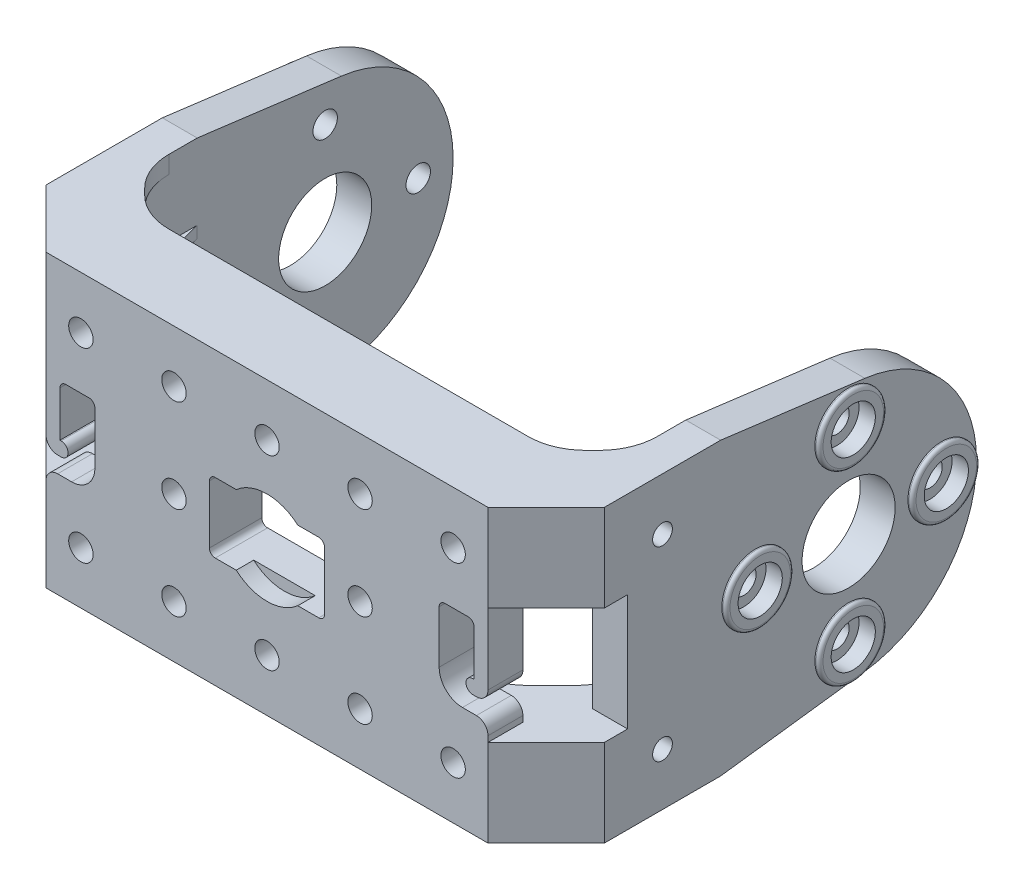
SolidWorks part; units mm, degrees
material "ABS PC"
ref_plane "Front Plane" through (0, 0, 0) normal (0, 0, 1) x (1, 0, 0)
ref_plane "Top Plane" through (0, 0, 0) normal (0, 1, 0) x (1, 0, 0)
ref_plane "Right Plane" through (0, 0, 0) normal (1, 0, 0) x (0, 0, -1)
ref_plane "Plane1" through (0, 0, 23) normal (0, 0, 1) x (1, 0, 0)
sketch "Sketch1" plane through (0, 0, 23) normal (0, 0, 1) x (1, 0, 0)
  line L0 (-14.5956, -5) -> (10.0809, -5)
  line L1 (10.0809, -5) -> (10.0809, -2.4936)
  line L2 (10.0809, -2.4936) -> (11.2, -1.8475)
  line L3 (11.2, -1.8475) -> (11.2, 1.8475)
  line L4 (11.2, 1.8475) -> (10.0809, 2.4936)
  line L5 (10.0809, 2.4936) -> (10.0809, 3.5)
  line L6 (10.0809, 3.5) -> (14.5956, 5)
  line L7 (14.5956, 5) -> (-14.5956, 5)
  line L8 (-14.5956, 5) -> (-10.0809, 3.5)
  line L9 (-10.0809, 3.5) -> (-10.0809, 2.4936)
  line L10 (-10.0809, 2.4936) -> (-11.2, 1.8475)
  line L11 (-11.2, 1.8475) -> (-11.2, -1.8475)
  line L12 (-11.2, -1.8475) -> (-10.0809, -2.4936)
  line L13 (-10.0809, -2.4936) -> (-10.0809, -3.5)
  line L14 (-10.0809, -3.5) -> (-14.5956, -5)
extrude "Boss-Extrude1" add sketch "Sketch1" against normal blind 1
sketch "Sketch2" plane through (0, 0, 22) normal (0, 0, -1) x (-1, 0, 0)
  line L0 (-10.0809, -5) -> (-10.0809, 3.5)
  line L1 (-10.0809, 3.5) -> (-14.5956, 5)
  line L2 (-14.5956, 5) -> (14.5956, 5)
  line L3 (14.5956, 5) -> (10.0809, 3.5)
  line L4 (10.0809, 3.5) -> (10.0809, -3.5)
  line L5 (10.0809, -3.5) -> (14.5956, -5)
  line L6 (14.5956, -5) -> (-10.0809, -5)
extrude "Boss-Extrude2" add sketch "Sketch2" along normal blind 0.5
sketch "Sketch3" plane through (0, 0, 23) normal (0, 0, 1) x (1, 0, 0)
  line L0 (-8.3378, -3.5) -> (-10.0809, -2.4936)
  line L1 (-10.0809, -2.4936) -> (-10.0809, -3.5)
  line L2 (-10.0809, -3.5) -> (-8.3378, -3.5)
extrude "Cut-Extrude1" cut sketch "Sketch3" against normal blind 1
sketch "Sketch4" plane through (0, 0, 23) normal (0, 0, 1) x (1, 0, 0)
  line L0 (-10.0809, 2.4936) -> (-8.3378, 3.5)
  line L1 (-8.3378, 3.5) -> (-10.0809, 3.5)
  line L2 (-10.0809, 3.5) -> (-10.0809, 2.4936)
extrude "Cut-Extrude2" cut sketch "Sketch4" against normal blind 1
sketch "Sketch5" plane through (0, 0, 23) normal (0, 0, 1) x (1, 0, 0)
  line L0 (10.0809, -2.4936) -> (8.3378, -3.5)
  line L1 (8.3378, -3.5) -> (10.0809, -3.5)
  line L2 (10.0809, -3.5) -> (10.0809, -2.4936)
extrude "Cut-Extrude3" cut sketch "Sketch5" against normal blind 1
sketch "Sketch6" plane through (10.0809, 0, 0) normal (1, 0, 0) x (0, 0, -1)
  line L0 (-23, -5) -> (-23, -3.5)
  line L1 (-23, -3.5) -> (-21.5, -3.5)
  line L2 (-21.5, -3.5) -> (-21.5, -5)
  line L3 (-21.5, -5) -> (-23, -5)
extrude "Boss-Extrude3" add sketch "Sketch6" along normal blind 10.9191
sketch "Sketch7" plane through (0, 0, 23) normal (0, 0, 1) x (1, 0, 0)
  line L0 (8.3378, 3.5) -> (10.0809, 2.4936)
  line L1 (10.0809, 2.4936) -> (10.0809, 3.5)
  line L2 (10.0809, 3.5) -> (8.3378, 3.5)
extrude "Cut-Extrude4" cut sketch "Sketch7" against normal blind 1
sketch "Sketch8" plane through (0, -5, 0) normal (0, -1, 0) x (1, 0, 0)
  line L0 (-21, 11) -> (-21, 23)
  line L1 (-21, 23) -> (21, 23)
  line L2 (21, 23) -> (21, 11)
  line L3 (21, 11) -> (19.5, 17.0147)
  line L4 (19.5, 17.0147) -> (17.5147, 19)
  line L5 (17.5147, 19) -> (-17.5147, 19)
  line L6 (-17.5147, 19) -> (-19.5, 17.0147)
  line L7 (-19.5, 17.0147) -> (-21, 11)
extrude "Boss-Extrude4" add sketch "Sketch8" along normal blind 7.5
sketch "Sketch9" plane through (0, 5, 0) normal (0, 1, 0) x (-1, 0, 0)
  line L0 (21, 23) -> (21, 11)
  line L1 (21, 11) -> (19.5, 17.0147)
  line L2 (19.5, 17.0147) -> (17.5147, 19)
  line L3 (17.5147, 19) -> (-17.5147, 19)
  line L4 (-17.5147, 19) -> (-19.5, 17.0147)
  line L5 (-19.5, 17.0147) -> (-21, 11)
  line L6 (-21, 11) -> (-21, 23)
  line L7 (-21, 23) -> (21, 23)
extrude "Boss-Extrude5" add sketch "Sketch9" along normal blind 7.5
sketch "Sketch10" plane through (0, -5, 0) normal (0, 1, 0) x (-1, 0, 0)
  line L0 (-17.5147, 19) -> (17.5147, 19)
  line L1 (17.5147, 19) -> (15.0147, 21.5)
  line L2 (15.0147, 21.5) -> (-15.0147, 21.5)
  line L3 (-15.0147, 21.5) -> (-17.5147, 19)
extrude "Cut-Extrude5" cut sketch "Sketch10" against normal blind 6
sketch "Sketch11" plane through (0, 5, 0) normal (0, -1, 0) x (1, 0, 0)
  line L0 (-17.5147, 19) -> (17.5147, 19)
  line L1 (17.5147, 19) -> (15.0147, 21.5)
  line L2 (15.0147, 21.5) -> (-15.0147, 21.5)
  line L3 (-15.0147, 21.5) -> (-17.5147, 19)
extrude "Cut-Extrude6" cut sketch "Sketch11" against normal blind 6
sketch "Sketch12" plane through (-21, 0, 0) normal (-1, 0, 0) x (0, 0, 1)
  line L0 (23, 12.5) -> (23, 5)
  line L1 (23, 5) -> (19, 5)
  line L2 (19, 5) -> (19, -5)
  line L3 (19, -5) -> (23, -5)
  line L4 (23, -5) -> (23, -12.5)
  line L5 (23, -12.5) -> (11, -12.5)
  line L6 (11, -12.5) -> (-1.3986, -10.9107)
  line L7 (-1.3986, 10.9107) -> (11, 12.5)
  line L8 (11, 12.5) -> (23, 12.5)
  arc A0 (-1.3986, -10.9107) -> (-1.3986, 10.9107) centre (0, 0) cw
extrude "Boss-Extrude6" add sketch "Sketch12" along normal blind 3
sketch "Sketch13" plane through (21, 0, 0) normal (1, 0, 0) x (0, 0, -1)
  line L0 (-23, 12.5) -> (-11, 12.5)
  line L1 (-11, 12.5) -> (1.3986, 10.9107)
  line L2 (1.3986, -10.9107) -> (-11, -12.5)
  line L3 (-11, -12.5) -> (-23, -12.5)
  line L4 (-23, -12.5) -> (-23, -3.5)
  line L5 (-23, -3.5) -> (-21.5, -3.5)
  line L6 (-21.5, -3.5) -> (-21.5, -5)
  line L7 (-21.5, -5) -> (-19, -5)
  line L8 (-19, -5) -> (-19, 5)
  line L9 (-19, 5) -> (-23, 5)
  line L10 (-23, 5) -> (-23, 12.5)
  arc A0 (1.3986, 10.9107) -> (1.3986, -10.9107) centre (0, 0) cw
extrude "Boss-Extrude7" add sketch "Sketch13" along normal blind 3
sketch "Sketch14" plane through (0, 12.5, 0) normal (0, 1, 0) x (-1, 0, 0)
  line L0 (21, 11) -> (21, 15.5147)
  line L1 (21, 15.5147) -> (19.5, 17.0147)
  line L2 (19.5, 17.0147) -> (21, 11)
extrude "Cut-Extrude7" cut sketch "Sketch14" against normal blind 1.5
sketch "Sketch15" plane through (0, 12.5, 0) normal (0, 1, 0) x (-1, 0, 0)
  line L0 (-21, 11) -> (-19.5, 17.0147)
  line L1 (-19.5, 17.0147) -> (-21, 15.5147)
  line L2 (-21, 15.5147) -> (-21, 11)
extrude "Cut-Extrude8" cut sketch "Sketch15" against normal blind 1.5
sketch "Sketch16" plane through (0, 11, 0) normal (0, 1, 0) x (-1, 0, 0)
  line L0 (21, 22) -> (-21, 22)
  line L1 (-21, 22) -> (-21, 11)
  line L2 (-21, 11) -> (-19.5, 17.0147)
  line L3 (-19.5, 17.0147) -> (-15.0147, 21.5)
  line L4 (-15.0147, 21.5) -> (15.0147, 21.5)
  line L5 (15.0147, 21.5) -> (19.5, 17.0147)
  line L6 (19.5, 17.0147) -> (21, 11)
  line L7 (21, 11) -> (21, 22)
extrude "Cut-Extrude9" cut sketch "Sketch16" against normal blind 5
sketch "Sketch17" plane through (10.0809, 0, 0) normal (1, 0, 0) x (0, 0, -1)
  line L0 (-21.5, 3.5) -> (-22, 3.5)
  line L1 (-22, 3.5) -> (-22, -3.5)
  line L2 (-22, -3.5) -> (-21.5, -3.5)
  line L3 (-21.5, -3.5) -> (-21.5, 3.5)
extrude "Cut-Extrude10" cut sketch "Sketch17" against normal blind 1.7431
sketch "Sketch18" plane through (0, -12.5, 0) normal (0, -1, 0) x (1, 0, 0)
  line L0 (-19.5, 17.0147) -> (-21, 15.5147)
  line L1 (-21, 15.5147) -> (-21, 11)
  line L2 (-21, 11) -> (-19.5, 17.0147)
extrude "Cut-Extrude11" cut sketch "Sketch18" against normal blind 1.5
sketch "Sketch19" plane through (0, -12.5, 0) normal (0, -1, 0) x (1, 0, 0)
  line L0 (21, 15.5147) -> (19.5, 17.0147)
  line L1 (19.5, 17.0147) -> (21, 11)
  line L2 (21, 11) -> (21, 15.5147)
extrude "Cut-Extrude12" cut sketch "Sketch19" against normal blind 1.5
sketch "Sketch20" plane through (0, -11, 0) normal (0, -1, 0) x (1, 0, 0)
  line L0 (21, 22) -> (-21, 22)
  line L1 (-21, 22) -> (-21, 11)
  line L2 (-21, 11) -> (-19.5, 17.0147)
  line L3 (-19.5, 17.0147) -> (-15.0147, 21.5)
  line L4 (-15.0147, 21.5) -> (15.0147, 21.5)
  line L5 (15.0147, 21.5) -> (19.5, 17.0147)
  line L6 (19.5, 17.0147) -> (21, 11)
  line L7 (21, 11) -> (21, 22)
extrude "Cut-Extrude13" cut sketch "Sketch20" against normal blind 5
sketch "Sketch21" plane through (8.3378, 0, 0) normal (1, 0, 0) x (0, 0, -1)
  line L0 (-21.5, 3.5) -> (-22, 3.5)
  line L1 (-22, 3.5) -> (-22, -3.5)
  line L2 (-22, -3.5) -> (-21.5, -3.5)
  line L3 (-21.5, -3.5) -> (-21.5, 3.5)
extrude "Cut-Extrude14" cut sketch "Sketch21" against normal blind 2.3378
sketch "Sketch22" plane through (-10.0809, 0, 0) normal (-1, 0, 0) x (0, 0, 1)
  line L0 (21.5, -3.5) -> (22, -3.5)
  line L1 (22, -3.5) -> (22, 3.5)
  line L2 (22, 3.5) -> (21.5, 3.5)
  line L3 (21.5, 3.5) -> (21.5, -3.5)
extrude "Cut-Extrude15" cut sketch "Sketch22" against normal blind 1.7431
sketch "Sketch23" plane through (24, 0, 0) normal (1, 0, 0) x (0, 0, -1)
  line L0 (-21.5, -3.5) -> (-23, -3.5)
  line L1 (-23, -3.5) -> (-23, -5)
  line L2 (-23, -5) -> (-21.5, -5)
  line L3 (-21.5, -5) -> (-21.5, -3.5)
extrude "Cut-Extrude16" cut sketch "Sketch23" against normal blind 8.9853
sketch "Sketch24" plane through (-8.3378, 0, 0) normal (-1, 0, 0) x (0, 0, 1)
  line L0 (21.5, -3.5) -> (22, -3.5)
  line L1 (22, -3.5) -> (22, 3.5)
  line L2 (22, 3.5) -> (21.5, 3.5)
  line L3 (21.5, 3.5) -> (21.5, -3.5)
extrude "Cut-Extrude17" cut sketch "Sketch24" against normal blind 2.3378
sketch "Sketch25" plane through (15.0147, 0, 0) normal (1, 0, 0) x (0, 0, -1)
  line L0 (-21.5, -3.5) -> (-23, -3.5)
  line L1 (-23, -3.5) -> (-23, -5)
  line L2 (-23, -5) -> (-21.5, -5)
  line L3 (-21.5, -5) -> (-21.5, -3.5)
extrude "Cut-Extrude18" cut sketch "Sketch25" against normal blind 0.4191
sketch "Sketch26" plane through (0, 0, 23) normal (0, 0, 1) x (1, 0, 0)
  line L0 (14.8, 3.5) -> (14.8, -3.5)
  line L1 (14.8, -3.5) -> (19, -3.5)
  line L2 (19, -3.5) -> (19, -5)
  line L3 (19, -5) -> (24, -5)
  line L4 (24, -5) -> (24, -12.5)
  line L5 (24, -12.5) -> (-24, -12.5)
  line L6 (-24, -12.5) -> (-24, -5)
  line L7 (-24, -5) -> (-19, -5)
  line L8 (-19, -5) -> (-19, -3.5)
  line L9 (-19, -3.5) -> (-14.8, -3.5)
  line L10 (-14.8, -3.5) -> (-14.8, 3.5)
  line L11 (-14.8, 3.5) -> (-17.8, 3.5)
  line L12 (-17.8, 3.5) -> (-17.8, -0.9)
  line L13 (-17.8, -0.9) -> (-17.7, -0.9)
  line L14 (-17.7, -2.1) -> (-19, -2.1)
  line L15 (-19, -2.1) -> (-19, 5)
  line L16 (-19, 5) -> (-24, 5)
  line L17 (-24, 5) -> (-24, 12.5)
  line L18 (-24, 12.5) -> (24, 12.5)
  line L19 (24, 12.5) -> (24, 5)
  line L20 (24, 5) -> (19, 5)
  line L21 (19, 5) -> (19, -2.1)
  line L22 (19, -2.1) -> (17.7, -2.1)
  line L23 (17.7, -0.9) -> (17.8, -0.9)
  line L24 (17.8, -0.9) -> (17.8, 3.5)
  line L25 (17.8, 3.5) -> (14.8, 3.5)
  arc A0 (-17.7, -0.9) -> (-17.7, -2.1) centre (-17.7, -1.5) cw
  arc A1 (17.7, -2.1) -> (17.7, -0.9) centre (17.7, -1.5) cw
extrude "Boss-Extrude8" add sketch "Sketch26" along normal blind 3
sketch "Sketch27" plane through (0, 0, 21.5) normal (0, 0, -1) x (-1, 0, 0)
  line L0 (-9.9191, 4.5) -> (9.9191, 4.5)
  line L1 (9.9191, 4.5) -> (14.4338, 6)
  line L2 (14.4338, 6) -> (-14.4338, 6)
  line L3 (-14.4338, 6) -> (-9.9191, 4.5)
extrude "Cut-Extrude19" cut sketch "Sketch27" against normal blind 0.5
sketch "Sketch28" plane through (0, 0, 22) normal (0, 0, -1) x (-1, 0, 0)
  line L0 (9.9191, 4.5) -> (13.8102, 5.7928)
  line L1 (13.8102, 5.7928) -> (12.5359, 8)
  line L2 (12.5359, 8) -> (14.2679, 11)
  line L3 (14.2679, 11) -> (9.2038, 11)
  line L4 (9.2038, 11) -> (11.2, 9.8475)
  line L5 (11.2, 9.8475) -> (11.2, 6.1525)
  line L6 (11.2, 6.1525) -> (8.3378, 4.5)
  line L7 (8.3378, 4.5) -> (9.9191, 4.5)
extrude "Cut-Extrude20" cut sketch "Sketch28" against normal blind 1
sketch "Sketch29" plane through (0, 0, 22) normal (0, 0, -1) x (-1, 0, 0)
  line L0 (7.6622, 4.5) -> (4.8, 6.1525)
  line L1 (4.8, 6.1525) -> (4.8, 9.8475)
  line L2 (4.8, 9.8475) -> (6.7962, 11)
  line L3 (6.7962, 11) -> (1.2038, 11)
  line L4 (1.2038, 11) -> (3.2, 9.8475)
  line L5 (3.2, 9.8475) -> (3.2, 6.1525)
  line L6 (3.2, 6.1525) -> (0.3378, 4.5)
  line L7 (0.3378, 4.5) -> (7.6622, 4.5)
extrude "Cut-Extrude21" cut sketch "Sketch29" against normal blind 1
sketch "Sketch30" plane through (0, 0, 22) normal (0, 0, -1) x (-1, 0, 0)
  line L0 (-8.3378, 4.5) -> (-11.2, 6.1525)
  line L1 (-11.2, 6.1525) -> (-11.2, 9.8475)
  line L2 (-11.2, 9.8475) -> (-9.2038, 11)
  line L3 (-9.2038, 11) -> (-14.2679, 11)
  line L4 (-14.2679, 11) -> (-12.5359, 8)
  line L5 (-12.5359, 8) -> (-13.8102, 5.7928)
  line L6 (-13.8102, 5.7928) -> (-9.9191, 4.5)
  line L7 (-9.9191, 4.5) -> (-8.3378, 4.5)
extrude "Cut-Extrude22" cut sketch "Sketch30" against normal blind 1
sketch "Sketch31" plane through (0, 0, 21.5) normal (0, 0, -1) x (-1, 0, 0)
  line L0 (9.9191, -4.5) -> (-9.9191, -4.5)
  line L1 (-9.9191, -4.5) -> (-14.4338, -6)
  line L2 (-14.4338, -6) -> (14.4338, -6)
  line L3 (14.4338, -6) -> (9.9191, -4.5)
extrude "Cut-Extrude23" cut sketch "Sketch31" against normal blind 0.5
sketch "Sketch32" plane through (0, 0, 22) normal (0, 0, -1) x (-1, 0, 0)
  line L0 (-7.6622, -4.5) -> (-4.8, -6.1525)
  line L1 (-4.8, -6.1525) -> (-4.8, -9.8475)
  line L2 (-4.8, -9.8475) -> (-6.7962, -11)
  line L3 (-6.7962, -11) -> (-1.2038, -11)
  line L4 (-1.2038, -11) -> (-3.2, -9.8475)
  line L5 (-3.2, -9.8475) -> (-3.2, -6.1525)
  line L6 (-3.2, -6.1525) -> (-0.3378, -4.5)
  line L7 (-0.3378, -4.5) -> (-7.6622, -4.5)
extrude "Cut-Extrude24" cut sketch "Sketch32" against normal blind 1
sketch "Sketch33" plane through (0, 0, 22) normal (0, 0, -1) x (-1, 0, 0)
  line L0 (-9.9191, -4.5) -> (-13.8102, -5.7928)
  line L1 (-13.8102, -5.7928) -> (-12.5359, -8)
  line L2 (-12.5359, -8) -> (-14.2679, -11)
  line L3 (-14.2679, -11) -> (-9.2038, -11)
  line L4 (-9.2038, -11) -> (-11.2, -9.8475)
  line L5 (-11.2, -9.8475) -> (-11.2, -6.1525)
  line L6 (-11.2, -6.1525) -> (-8.3378, -4.5)
  line L7 (-8.3378, -4.5) -> (-9.9191, -4.5)
extrude "Cut-Extrude25" cut sketch "Sketch33" against normal blind 1
sketch "Sketch34" plane through (0, 0, 22) normal (0, 0, -1) x (-1, 0, 0)
  line L0 (-0.3378, 4.5) -> (-3.2, 6.1525)
  line L1 (-3.2, 6.1525) -> (-3.2, 9.8475)
  line L2 (-3.2, 9.8475) -> (-1.2038, 11)
  line L3 (-1.2038, 11) -> (-6.7962, 11)
  line L4 (-6.7962, 11) -> (-4.8, 9.8475)
  line L5 (-4.8, 9.8475) -> (-4.8, 6.1525)
  line L6 (-4.8, 6.1525) -> (-7.6622, 4.5)
  line L7 (-7.6622, 4.5) -> (-0.3378, 4.5)
extrude "Cut-Extrude26" cut sketch "Sketch34" against normal blind 1
sketch "Sketch35" plane through (0, 0, 22) normal (0, 0, -1) x (-1, 0, 0)
  line L0 (8.3378, -4.5) -> (11.2, -6.1525)
  line L1 (11.2, -6.1525) -> (11.2, -9.8475)
  line L2 (11.2, -9.8475) -> (9.2038, -11)
  line L3 (9.2038, -11) -> (14.2679, -11)
  line L4 (14.2679, -11) -> (12.5359, -8)
  line L5 (12.5359, -8) -> (13.8102, -5.7928)
  line L6 (13.8102, -5.7928) -> (9.9191, -4.5)
  line L7 (9.9191, -4.5) -> (8.3378, -4.5)
extrude "Cut-Extrude27" cut sketch "Sketch35" against normal blind 1
sketch "Sketch36" plane through (0, 0, 22) normal (0, 0, -1) x (-1, 0, 0)
  line L0 (0.3378, -4.5) -> (3.2, -6.1525)
  line L1 (3.2, -6.1525) -> (3.2, -9.8475)
  line L2 (3.2, -9.8475) -> (1.2038, -11)
  line L3 (1.2038, -11) -> (6.7962, -11)
  line L4 (6.7962, -11) -> (4.8, -9.8475)
  line L5 (4.8, -9.8475) -> (4.8, -6.1525)
  line L6 (4.8, -6.1525) -> (7.6622, -4.5)
  line L7 (7.6622, -4.5) -> (0.3378, -4.5)
extrude "Cut-Extrude28" cut sketch "Sketch36" against normal blind 1
sketch "Sketch37" plane through (0, 0, 22) normal (0, 0, -1) x (-1, 0, 0)
  line L0 (-13.6906, -8) -> (-14.8453, -6)
  line L1 (-14.8453, -6) -> (-17.1547, -6)
  line L2 (-17.1547, -6) -> (-18.3094, -8)
  line L3 (-18.3094, -8) -> (-17.1547, -10)
  line L4 (-17.1547, -10) -> (-14.8453, -10)
  line L5 (-14.8453, -10) -> (-13.6906, -8)
extrude "Cut-Extrude29" cut sketch "Sketch37" against normal blind 2
sketch "Sketch38" plane through (0, 0, 22) normal (0, 0, -1) x (-1, 0, 0)
  line L0 (-17.7321, -11) -> (-19.4641, -8)
  line L1 (-19.4641, -8) -> (-18.3094, -6)
  line L2 (-18.3094, -6) -> (-21, -6)
  line L3 (-21, -6) -> (-21, -11)
  line L4 (-21, -11) -> (-17.7321, -11)
extrude "Cut-Extrude30" cut sketch "Sketch38" against normal blind 1
sketch "Sketch39" plane through (0, 0, 22) normal (0, 0, -1) x (-1, 0, 0)
  line L0 (-14.8453, 10) -> (-17.1547, 10)
  line L1 (-17.1547, 10) -> (-18.3094, 8)
  line L2 (-18.3094, 8) -> (-17.1547, 6)
  line L3 (-17.1547, 6) -> (-14.8453, 6)
  line L4 (-14.8453, 6) -> (-13.6906, 8)
  line L5 (-13.6906, 8) -> (-14.8453, 10)
extrude "Cut-Extrude31" cut sketch "Sketch39" against normal blind 2
sketch "Sketch40" plane through (0, 0, 22) normal (0, 0, -1) x (-1, 0, 0)
  line L0 (-17.7321, 11) -> (-21, 11)
  line L1 (-21, 11) -> (-21, 6)
  line L2 (-21, 6) -> (-18.3094, 6)
  line L3 (-18.3094, 6) -> (-19.4641, 8)
  line L4 (-19.4641, 8) -> (-17.7321, 11)
extrude "Cut-Extrude32" cut sketch "Sketch40" against normal blind 1
sketch "Sketch41" plane through (0, 0, 22) normal (0, 0, -1) x (-1, 0, 0)
  line L0 (13.6906, 8) -> (14.8453, 6)
  line L1 (14.8453, 6) -> (17.1547, 6)
  line L2 (17.1547, 6) -> (18.3094, 8)
  line L3 (18.3094, 8) -> (17.1547, 10)
  line L4 (17.1547, 10) -> (14.8453, 10)
  line L5 (14.8453, 10) -> (13.6906, 8)
extrude "Cut-Extrude33" cut sketch "Sketch41" against normal blind 2
sketch "Sketch42" plane through (0, 0, 22) normal (0, 0, -1) x (-1, 0, 0)
  line L0 (17.7321, 11) -> (19.4641, 8)
  line L1 (19.4641, 8) -> (18.3094, 6)
  line L2 (18.3094, 6) -> (21, 6)
  line L3 (21, 6) -> (21, 11)
  line L4 (21, 11) -> (17.7321, 11)
extrude "Cut-Extrude34" cut sketch "Sketch42" against normal blind 1
sketch "Sketch43" plane through (0, 0, 22) normal (0, 0, -1) x (-1, 0, 0)
  line L0 (14.8453, -10) -> (17.1547, -10)
  line L1 (17.1547, -10) -> (18.3094, -8)
  line L2 (18.3094, -8) -> (17.1547, -6)
  line L3 (17.1547, -6) -> (14.8453, -6)
  line L4 (14.8453, -6) -> (13.6906, -8)
  line L5 (13.6906, -8) -> (14.8453, -10)
extrude "Cut-Extrude35" cut sketch "Sketch43" against normal blind 2
sketch "Sketch44" plane through (0, 0, 22) normal (0, 0, -1) x (-1, 0, 0)
  line L0 (17.7321, -11) -> (21, -11)
  line L1 (21, -11) -> (21, -6)
  line L2 (21, -6) -> (18.3094, -6)
  line L3 (18.3094, -6) -> (19.4641, -8)
  line L4 (19.4641, -8) -> (17.7321, -11)
extrude "Cut-Extrude36" cut sketch "Sketch44" against normal blind 1
sketch "Sketch45" plane through (0, 0, 22) normal (0, 0, -1) x (-1, 0, 0)
  line L0 (-8, 2.3094) -> (-10, 1.1547)
  line L1 (-10, 1.1547) -> (-10, -1.1547)
  line L2 (-10, -1.1547) -> (-8, -2.3094)
  line L3 (-8, -2.3094) -> (-6, -1.1547)
  line L4 (-6, -1.1547) -> (-6, 1.1547)
  line L5 (-6, 1.1547) -> (-8, 2.3094)
extrude "Cut-Extrude37" cut sketch "Sketch45" against normal blind 2
sketch "Sketch46" plane through (0, 0, 22) normal (0, 0, -1) x (-1, 0, 0)
  line L0 (-6, 3.5) -> (-7.6622, 3.5)
  line L1 (-7.6622, 3.5) -> (-6, 2.5403)
  line L2 (-6, 2.5403) -> (-6, 3.5)
extrude "Cut-Extrude38" cut sketch "Sketch46" against normal blind 1
sketch "Sketch47" plane through (0, 0, 22) normal (0, 0, -1) x (-1, 0, 0)
  line L0 (-6, -2.5403) -> (-7.6622, -3.5)
  line L1 (-7.6622, -3.5) -> (-6, -3.5)
  line L2 (-6, -3.5) -> (-6, -2.5403)
extrude "Cut-Extrude39" cut sketch "Sketch47" against normal blind 1
sketch "Sketch48" plane through (0, 0, 22) normal (0, 0, -1) x (-1, 0, 0)
  line L0 (8, 2.3094) -> (6, 1.1547)
  line L1 (6, 1.1547) -> (6, -1.1547)
  line L2 (6, -1.1547) -> (8, -2.3094)
  line L3 (8, -2.3094) -> (10, -1.1547)
  line L4 (10, -1.1547) -> (10, 1.1547)
  line L5 (10, 1.1547) -> (8, 2.3094)
extrude "Cut-Extrude40" cut sketch "Sketch48" against normal blind 2
sketch "Sketch49" plane through (0, 0, 22) normal (0, 0, -1) x (-1, 0, 0)
  line L0 (6, -3.5) -> (7.6622, -3.5)
  line L1 (7.6622, -3.5) -> (6, -2.5403)
  line L2 (6, -2.5403) -> (6, -3.5)
extrude "Cut-Extrude41" cut sketch "Sketch49" against normal blind 1
sketch "Sketch50" plane through (0, 0, 22) normal (0, 0, -1) x (-1, 0, 0)
  line L0 (6, 2.5403) -> (7.6622, 3.5)
  line L1 (7.6622, 3.5) -> (6, 3.5)
  line L2 (6, 3.5) -> (6, 2.5403)
extrude "Cut-Extrude42" cut sketch "Sketch50" against normal blind 1
sketch "Sketch51" plane through (0, 0, 26) normal (0, 0, 1) x (1, 0, 0)
  line L0 (-4.95, 3) -> (-4.95, -3)
  line L1 (-4.95, -3) -> (4.95, -3)
  line L2 (4.95, -3) -> (4.95, 3)
  line L3 (4.95, 3) -> (-4.95, 3)
extrude "Cut-Extrude43" cut sketch "Sketch51" against normal through all
sketch "Sketch52" plane through (0, 0, 26) normal (0, 0, 1) x (1, 0, 0)
  line L0 (2.6458, -3) -> (-2.6458, -3)
  arc A0 (-2.6458, -3) -> (2.6458, -3) centre (0, 0) ccw
extrude "Cut-Extrude44" cut sketch "Sketch52" against normal blind 1.5
sketch "Sketch53" plane through (0, 0, 26) normal (0, 0, 1) x (1, 0, 0)
  line L0 (-2.6458, 3) -> (2.6458, 3)
  arc A0 (2.6458, 3) -> (-2.6458, 3) centre (0, 0) ccw
extrude "Cut-Extrude45" cut sketch "Sketch53" against normal blind 1.5
sketch "Sketch54" plane through (0, 0, 22) normal (0, 0, -1) x (-1, 0, 0)
  line L0 (2, -6.8453) -> (0, -5.6906)
  line L1 (0, -5.6906) -> (-2, -6.8453)
  line L2 (-2, -6.8453) -> (-2, -9.1547)
  line L3 (-2, -9.1547) -> (0, -10.3094)
  line L4 (0, -10.3094) -> (2, -9.1547)
  line L5 (2, -9.1547) -> (2, -6.8453)
extrude "Cut-Extrude46" cut sketch "Sketch54" against normal blind 2
sketch "Sketch55" plane through (0, 0, 22) normal (0, 0, -1) x (-1, 0, 0)
  line L0 (-6, 9.1547) -> (-8, 10.3094)
  line L1 (-8, 10.3094) -> (-10, 9.1547)
  line L2 (-10, 9.1547) -> (-10, 6.8453)
  line L3 (-10, 6.8453) -> (-8, 5.6906)
  line L4 (-8, 5.6906) -> (-6, 6.8453)
  line L5 (-6, 6.8453) -> (-6, 9.1547)
extrude "Cut-Extrude47" cut sketch "Sketch55" against normal blind 2
sketch "Sketch56" plane through (0, 0, 22) normal (0, 0, -1) x (-1, 0, 0)
  line L0 (2, 9.1547) -> (0, 10.3094)
  line L1 (0, 10.3094) -> (-2, 9.1547)
  line L2 (-2, 9.1547) -> (-2, 6.8453)
  line L3 (-2, 6.8453) -> (0, 5.6906)
  line L4 (0, 5.6906) -> (2, 6.8453)
  line L5 (2, 6.8453) -> (2, 9.1547)
extrude "Cut-Extrude48" cut sketch "Sketch56" against normal blind 2
sketch "Sketch57" plane through (0, 0, 22) normal (0, 0, -1) x (-1, 0, 0)
  line L0 (10, 9.1547) -> (8, 10.3094)
  line L1 (8, 10.3094) -> (6, 9.1547)
  line L2 (6, 9.1547) -> (6, 6.8453)
  line L3 (6, 6.8453) -> (8, 5.6906)
  line L4 (8, 5.6906) -> (10, 6.8453)
  line L5 (10, 6.8453) -> (10, 9.1547)
extrude "Cut-Extrude49" cut sketch "Sketch57" against normal blind 2
sketch "Sketch58" plane through (0, 0, 22) normal (0, 0, -1) x (-1, 0, 0)
  line L0 (10, -6.8453) -> (8, -5.6906)
  line L1 (8, -5.6906) -> (6, -6.8453)
  line L2 (6, -6.8453) -> (6, -9.1547)
  line L3 (6, -9.1547) -> (8, -10.3094)
  line L4 (8, -10.3094) -> (10, -9.1547)
  line L5 (10, -9.1547) -> (10, -6.8453)
extrude "Cut-Extrude50" cut sketch "Sketch58" against normal blind 2
sketch "Sketch59" plane through (0, 0, 22) normal (0, 0, -1) x (-1, 0, 0)
  line L0 (-6, -6.8453) -> (-8, -5.6906)
  line L1 (-8, -5.6906) -> (-10, -6.8453)
  line L2 (-10, -6.8453) -> (-10, -9.1547)
  line L3 (-10, -9.1547) -> (-8, -10.3094)
  line L4 (-8, -10.3094) -> (-6, -9.1547)
  line L5 (-6, -9.1547) -> (-6, -6.8453)
extrude "Cut-Extrude51" cut sketch "Sketch59" against normal blind 2
draft "Draft1" type of draft neutral plane draft angle 71.621 faces to draft 1 face at (14.5956, -4.25, 22.25) neutral plane through (0, -5, 0) neutral plane normal (0, 1, 0) parameters "D1"=71.621
sketch "Sketch60" plane through (0, 0, 0) normal (0, 0, 1) x (1, 0, 0)
  line L0 (24, 10.9) -> (24, 8)
  line L1 (24, 8) -> (24.4, 8)
  line L2 (24.4, 8) -> (24.4, 10.9)
  line L3 (24.4, 10.9) -> (24, 10.9)
  line L4 (24, 8) -> (24.4, 8) construction
revolve "Revolve1" add sketch "Sketch60" angle 360 about L4 reverse direction yes
ref_plane "Plane2" through (0, 0, -8) normal (0, 0, 1) x (1, 0, 0)
sketch "Sketch61" plane through (0, 0, -8) normal (0, 0, 1) x (1, 0, 0)
  line L0 (24, 2.9) -> (24, 0)
  line L1 (24, 0) -> (24.4, 0)
  line L2 (24.4, 0) -> (24.4, 2.9)
  line L3 (24.4, 2.9) -> (24, 2.9)
  line L4 (24, 0) -> (24.4, 0) construction
revolve "Revolve2" add sketch "Sketch61" angle 360 about L4 reverse direction yes
sketch "Sketch62" plane through (0, 0, 0) normal (0, 0, 1) x (1, 0, 0)
  line L0 (24, -5.1) -> (24, -8)
  line L1 (24, -8) -> (24.4, -8)
  line L2 (24.4, -8) -> (24.4, -5.1)
  line L3 (24.4, -5.1) -> (24, -5.1)
  line L4 (24, -8) -> (24.4, -8) construction
revolve "Revolve3" add sketch "Sketch62" angle 360 about L4 reverse direction yes
ref_plane "Plane3" through (0, 0, 8) normal (0, 0, 1) x (1, 0, 0)
sketch "Sketch63" plane through (0, 0, 8) normal (0, 0, 1) x (1, 0, 0)
  line L0 (24, 2.9) -> (24, 0)
  line L1 (24, 0) -> (24.4, 0)
  line L2 (24.4, 0) -> (24.4, 2.9)
  line L3 (24.4, 2.9) -> (24, 2.9)
  line L4 (24, 0) -> (24.4, 0) construction
revolve "Revolve4" add sketch "Sketch63" angle 360 about L4 reverse direction yes
ref_plane "Plane4" through (0, 0, -8) normal (0, 0, -1) x (-1, 0, 0)
sketch "Sketch64" plane through (0, 0, -8) normal (0, 0, -1) x (-1, 0, 0)
  line L0 (24, 2.9) -> (24, 0)
  line L1 (24, 0) -> (24.4, 0)
  line L2 (24.4, 0) -> (24.4, 2.9)
  line L3 (24.4, 2.9) -> (24, 2.9)
  line L4 (24, 0) -> (24.4, 0) construction
revolve "Revolve5" add sketch "Sketch64" angle 360 about L4 reverse direction yes
ref_plane "Plane5" through (0, 0, 0) normal (0, 0, -1) x (-1, 0, 0)
sketch "Sketch65" plane through (0, 0, 0) normal (0, 0, -1) x (-1, 0, 0)
  line L0 (24, 10.9) -> (24, 8)
  line L1 (24, 8) -> (24.4, 8)
  line L2 (24.4, 8) -> (24.4, 10.9)
  line L3 (24.4, 10.9) -> (24, 10.9)
  line L4 (24, 8) -> (24.4, 8) construction
revolve "Revolve6" add sketch "Sketch65" angle 360 about L4 reverse direction yes
ref_plane "Plane6" through (0, 0, 8) normal (0, 0, -1) x (-1, 0, 0)
sketch "Sketch66" plane through (0, 0, 8) normal (0, 0, -1) x (-1, 0, 0)
  line L0 (24, 2.9) -> (24, 0)
  line L1 (24, 0) -> (24.4, 0)
  line L2 (24.4, 0) -> (24.4, 2.9)
  line L3 (24.4, 2.9) -> (24, 2.9)
  line L4 (24, 0) -> (24.4, 0) construction
revolve "Revolve7" add sketch "Sketch66" angle 360 about L4 reverse direction yes
sketch "Sketch67" plane through (0, 0, 0) normal (0, 0, -1) x (-1, 0, 0)
  line L0 (24, -5.1) -> (24, -8)
  line L1 (24, -8) -> (24.4, -8)
  line L2 (24.4, -8) -> (24.4, -5.1)
  line L3 (24.4, -5.1) -> (24, -5.1)
  line L4 (24, -8) -> (24.4, -8) construction
revolve "Revolve8" add sketch "Sketch67" angle 360 about L4 reverse direction yes
hole_wizard "Ø1.7 (1.7) Diameter Hole1" positions "Sketch69" profile "Sketch68" hole size "Ø1.7" standard "ANSI Metric"
sketch "Sketch69" plane through (24, 0, 0) normal (1, 0, 0) x (0, 0, -1)
  point P0 (-16, -8)
  point P1 (-16, 8)
sketch "Sketch68" plane through (24, -8, 16) normal (0, 1, 0) x (0, 0, -1)
  line L0 (0, 0) -> (0, 3)
  line L1 (0, 3) -> (0.85, 3)
  line L2 (0.85, 3) -> (0.85, 0)
  line L5 (0.85, 0) -> (0, 0)
  line L11 (0, -6.35) -> (0, 107.95) construction
  dimension "Thru Hole Dia." = 1.7
  dimension "Thru Hole Depth" = 3
hole_wizard "Ø1.7 (1.7) Diameter Hole2" positions "Sketch71" profile "Sketch70" hole size "Ø1.7" standard "ANSI Metric"
sketch "Sketch71" plane through (-21, 0, 0) normal (1, 0, 0) x (0, 0, -1)
  point P0 (-16, -8)
  point P1 (-16, 8)
sketch "Sketch70" plane through (-21, -8, 16) normal (0, 1, 0) x (0, 0, -1)
  line L0 (0, 0) -> (0, 3.4)
  line L1 (0, 3.4) -> (0.85, 3.4)
  line L2 (0.85, 3.4) -> (0.85, 0)
  line L5 (0.85, 0) -> (0, 0)
  line L11 (0, -6.35) -> (0, 107.95) construction
  dimension "Thru Hole Dia." = 1.7
  dimension "Thru Hole Depth" = 3.4
hole_wizard "Ø2.1 (2.1) Diameter Hole1" positions "Sketch73" profile "Sketch72" hole size "Ø2.1" standard "ANSI Metric"
sketch "Sketch73" plane through (0, 0, 26) normal (0, 0, 1) x (1, 0, 0)
  point P0 (0, -8)
  point P1 (8, 8)
  point P2 (0, 8)
  point P3 (-8, 8)
  point P4 (-8, -8)
  point P5 (8, -8)
  point P6 (-16, 8)
  point P7 (8, 0)
  point P8 (16, 8)
  point P9 (16, -8)
  point P10 (-8, 0)
  point P11 (-16, -8)
sketch "Sketch72" plane through (0, -8, 26) normal (1, 0, 0) x (0, -1, 0)
  line L0 (0, 0) -> (0, 37)
  line L1 (0, 37) -> (1.05, 37)
  line L2 (1.05, 37) -> (1.05, 0)
  line L5 (1.05, 0) -> (0, 0)
  line L11 (0, -6.35) -> (0, 107.95) construction
  dimension "Thru Hole Dia." = 2.1
  dimension "Thru Hole Depth" = 37
hole_wizard "Hole1" positions "Sketch75" profile "Sketch74" legacy
sketch "Sketch75" plane through (24.4, 0, 0) normal (1, 0, 0) x (0, 0, -1)
  point P0 (-8, 0)
  point P1 (0, -8)
  point P2 (8, 0)
  point P3 (0, 8)
sketch "Sketch74" plane through (24.4, 0, 8) normal (0, 1, 0) x (0, 0, -1)
  line L0 (0, 0) -> (0, 3.4)
  line L1 (0, 3.4) -> (1.05, 3.4)
  line L2 (1.05, 3.4) -> (1.05, 1.4)
  line L3 (1.05, 1.4) -> (1.9, 1.4)
  line L4 (1.9, 1.4) -> (1.9, 0)
  line L5 (1.9, 0) -> (0, 0)
  line L6 (0, 110) -> (0, -10) construction
  dimension "Diameter" = 2.1
  dimension "Depth" = 3.4
  dimension "C-Bore Diameter" = 3.8
  dimension "C-Bore Depth" = 1.4
hole_wizard "Hole2" positions "Sketch77" profile "Sketch76" legacy
sketch "Sketch77" plane through (-24.4, 0, 0) normal (-1, 0, 0) x (0, 0, 1)
  point P0 (8, 0)
  point P1 (0, -8)
  point P2 (0, 8)
  point P3 (-8, 0)
sketch "Sketch76" plane through (-24.4, 0, 8) normal (0, 1, 0) x (0, 0, 1)
  line L0 (0, 0) -> (0, 48.8)
  line L1 (0, 48.8) -> (1.05, 48.8)
  line L2 (1.05, 48.8) -> (1.05, 1.4)
  line L3 (1.05, 1.4) -> (1.9, 1.4)
  line L4 (1.9, 1.4) -> (1.9, 0)
  line L5 (1.9, 0) -> (0, 0)
  line L6 (0, 110) -> (0, -10) construction
  dimension "Diameter" = 2.1
  dimension "Depth" = 48.8
  dimension "C-Bore Diameter" = 3.8
  dimension "C-Bore Depth" = 1.4
hole_wizard "Ø8.0 (8) Diameter Hole1" positions "Sketch79" profile "Sketch78" hole size "Ø8.0" standard "ANSI Metric"
sketch "Sketch79" plane through (24, 0, 0) normal (1, 0, 0) x (0, 0, -1)
  point P0 (0, 0)
sketch "Sketch78" plane through (24, 0, 0) normal (0, 1, 0) x (0, 0, -1)
  line L0 (0, 0) -> (0, 3)
  line L1 (0, 3) -> (4, 3)
  line L2 (4, 3) -> (4, 0)
  line L5 (4, 0) -> (0, 0)
  line L11 (0, -6.35) -> (0, 107.95) construction
  dimension "Thru Hole Dia." = 8
  dimension "Thru Hole Depth" = 3
hole_wizard "Ø8.0 (8) Diameter Hole2" positions "Sketch81" profile "Sketch80" hole size "Ø8.0" standard "ANSI Metric"
sketch "Sketch81" plane through (-21, 0, 0) normal (1, 0, 0) x (0, 0, -1)
  point P0 (0, 0)
sketch "Sketch80" plane through (-21, 0, 0) normal (0, 1, 0) x (0, 0, -1)
  line L0 (0, 0) -> (0, 3.4)
  line L1 (0, 3.4) -> (4, 3.4)
  line L2 (4, 3.4) -> (4, 0)
  line L5 (4, 0) -> (0, 0)
  line L11 (0, -6.35) -> (0, 107.95) construction
  dimension "Thru Hole Dia." = 8
  dimension "Thru Hole Depth" = 3.4
chamfer "Chamfer1" distance 5 angle 45 4 edges at (-24, 8.75, 26) (-24, -8.75, 26) (24, 8.75, 26) (24, -8.75, 26)
fillet "Fillet1" radius 0.3 8 edges at (24.4, -8, -2.9) (-24.4, 8, 2.9) (-24.4, 0, 10.9) (-24.4, -8, 2.9) (-24.4, 0, -5.1) (24.4, 0, -10.9) (24.4, 8, -2.9) (24.4, 0, 5.1) tangent propagation no
fillet "Fillet2" radius 0.5 8 edges at (-4.95, 3, 23.75) (17.8, 3.5, 24.5) (4.95, -3, 23.75) (-4.95, -3, 23.75) (14.8, 3.5, 24.5) (-17.8, 3.5, 24.5) (-14.8, 3.5, 24.5) (4.95, 3, 23.75) tangent propagation no
fillet "Fillet3" radius 1 4 edges at (19, -2.1, 24.5) (19, -3.5, 24.5) (-19, -3.5, 24.5) (-19, -2.1, 24.5) tangent propagation no
fillet "Fillet4" radius 2 2 edges at (14.8, -3.5, 24.5) (-14.8, -3.5, 24.5) tangent propagation no
fillet "Fillet5" radius 5 16 edges at (-15.0147, -5.5, 21.5) (15.0147, -5.5, 21.5) (-19.5, 5.5, 17.0147) (-19.5, -5.5, 17.0147) (15.0147, 5.5, 21.5) (21, -11.75, 15.5147) (-21, 11.75, 15.5147) (17.5147, -11.75, 19) (-15.0147, 5.5, 21.5) (-17.5147, -11.75, 19) (19.5, -5.5, 17.0147) (21, 11.75, 15.5147) (19.5, 5.5, 17.0147) (17.5147, 11.75, 19) (-17.5147, 11.75, 19) (-21, -11.75, 15.5147) tangent propagation no
